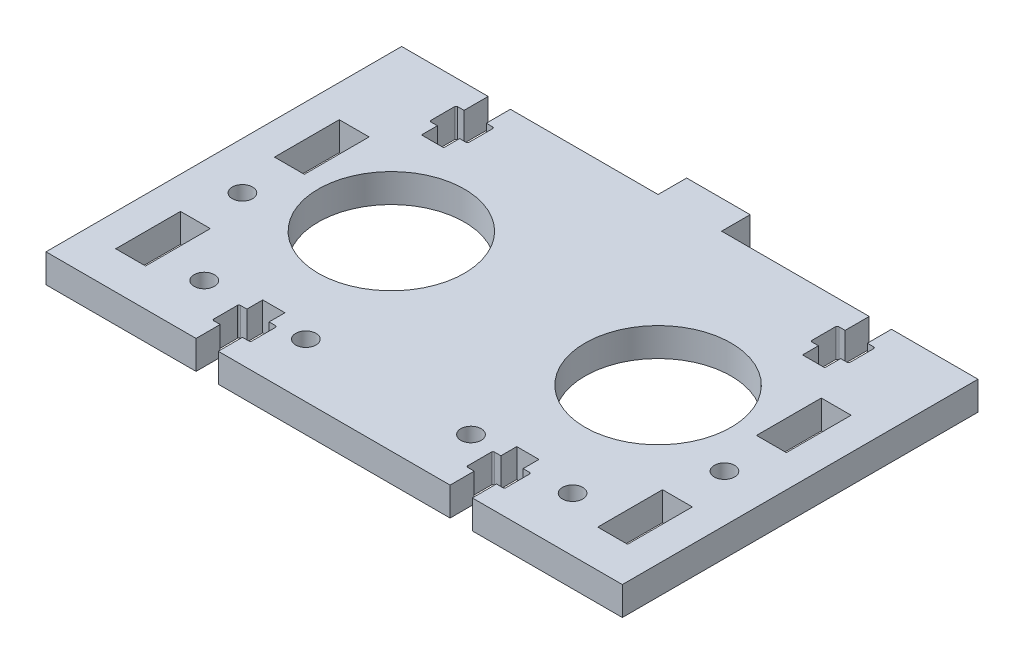
SolidWorks part; units mm, degrees
ref_plane "Front Plane" through (0, 0, 0) normal (0, 0, 1) x (1, 0, 0)
ref_plane "Top Plane" through (0, 0, 0) normal (0, 1, 0) x (1, 0, 0)
ref_plane "Right Plane" through (0, 0, 0) normal (1, 0, 0) x (0, 0, -1)
sketch "Sketch1" plane through (0, 0, 0) normal (0, 1, 0) x (1, 0, 0)
  line L1 (-45.375, 28) -> (45.375, 28)
  line L2 (-45.375, 28) -> (-45.375, -28)
  line L3 (-45.375, -28) -> (45.375, -28)
  line L4 (45.375, 28) -> (45.375, -28)
  line L5 (-45.375, 28) -> (45.375, -28) construction
  line L6 (-45.375, -28) -> (45.375, 28) construction
  point P0 (0, 0)
  dimension "D1" = 90.75
  dimension "D2" = 56
extrude "MainShape" add sketch "Sketch1" along normal blind 4.5
sketch "Sketch2" plane through (0, 4.5, 0) normal (0, 1, 0) x (1, 0, 0)
  line L0 (0, -28) -> (0, 28) construction
  line L1 (-45.375, -28) -> (45.375, -28) construction
  line L2 (45.375, 28) -> (-45.375, 28) construction
  line L4 (-5, 32.5) -> (5, 32.5)
  line L5 (-5, 32.5) -> (-5, 23.5)
  line L6 (-5, 23.5) -> (5, 23.5)
  line L7 (5, 32.5) -> (5, 23.5)
  line L8 (-5, 32.5) -> (5, 23.5) construction
  line L9 (-5, 23.5) -> (5, 32.5) construction
  dimension "D2" = 4.5
extrude "Tab1" add sketch "Sketch2" against normal through all
sketch "Sketch4" plane through (0, 4.5, 0) normal (0, 1, 0) x (1, 0, 0)
  line L0 (0, 32.5) -> (0, -28) construction
  line L1 (5, 32.5) -> (-5, 32.5) construction
  line L2 (-45.375, -28) -> (45.375, -28) construction
  line L3 (-30, 28) -> (-30, 17.5) construction
  line L4 (-5, 28) -> (-45.375, 28) construction
  line L5 (-28.25, 17.5) -> (-31.75, 17.5) construction
  line L6 (-31.75, 17.5) -> (-31.75, 28) construction
  line L7 (-28.25, 17.5) -> (-31.75, 17.5)
  line L8 (-31.75, 17.5) -> (-31.75, 20)
  line L9 (-31.75, 20) -> (-32.75, 20)
  line L10 (-33, 20.25) -> (-33, 23.95)
  line L11 (-32.75, 24.2) -> (-31.75, 24.2)
  line L12 (-31.75, 24.2) -> (-31.75, 28)
  line L13 (-31.75, 28) -> (-28.25, 28)
  line L14 (-28.25, 17.5) -> (-28.25, 28) construction
  line L15 (-28.25, 24.2) -> (-28.25, 28)
  line L16 (-27.25, 24.2) -> (-28.25, 24.2)
  line L17 (-27, 20.25) -> (-27, 23.95)
  line L18 (-28.25, 20) -> (-27.25, 20)
  line L19 (-28.25, 17.5) -> (-28.25, 20)
  line L20 (28.25, 17.5) -> (28.25, 28) construction
  line L21 (31.75, 17.5) -> (31.75, 28) construction
  line L22 (28.25, 17.5) -> (31.75, 17.5) construction
  line L23 (30, 28) -> (30, 17.5) construction
  line L24 (28.25, 17.5) -> (28.25, 20)
  line L25 (28.25, 20) -> (27.25, 20)
  line L26 (27, 20.25) -> (27, 23.95)
  line L27 (27.25, 24.2) -> (28.25, 24.2)
  line L28 (28.25, 24.2) -> (28.25, 28)
  line L29 (31.75, 28) -> (28.25, 28)
  line L30 (31.75, 24.2) -> (31.75, 28)
  line L31 (32.75, 24.2) -> (31.75, 24.2)
  line L32 (33, 20.25) -> (33, 23.95)
  line L33 (31.75, 20) -> (32.75, 20)
  line L34 (31.75, 17.5) -> (31.75, 20)
  line L35 (28.25, 17.5) -> (31.75, 17.5)
  arc A0 (-32.75, 20) -> (-33, 20.25) centre (-32.75, 20.25) cw
  arc A1 (-27, 20.25) -> (-27.25, 20) centre (-27.25, 20.25) cw
  arc A2 (-27.25, 24.2) -> (-27, 23.95) centre (-27.25, 23.95) cw
  arc A3 (-33, 23.95) -> (-32.75, 24.2) centre (-32.75, 23.95) cw
  arc A4 (33, 23.95) -> (32.75, 24.2) centre (32.75, 23.95) ccw
  arc A5 (27.25, 24.2) -> (27, 23.95) centre (27.25, 23.95) ccw
  arc A6 (27, 20.25) -> (27.25, 20) centre (27.25, 20.25) ccw
  arc A7 (32.75, 20) -> (33, 20.25) centre (32.75, 20.25) ccw
  point P24 (-33, 20)
  point P27 (-27, 20)
  point P30 (-27, 24.2)
  point P33 (-33, 24.2)
  point P56 (33, 24.2)
  point P57 (27, 24.2)
  point P58 (27, 20)
  point P59 (33, 20)
  dimension "D7" = 0.25
  dimension "D1" = 10.5
  dimension "D2" = 1.75
  dimension "D3" = 4.2
  dimension "D4" = 3
  dimension "D5" = 8
  dimension "D6" = 30
extrude "Cut-Extrude2" cut sketch "Sketch4" against normal through all
sketch "Sketch5" plane through (0, 4.5, 0) normal (0, 1, 0) x (1, 0, 0)
  line L0 (0, -28) -> (0, 32.5) construction
  line L1 (-45.375, -28) -> (45.375, -28) construction
  line L2 (5, 32.5) -> (-5, 32.5) construction
  line L3 (37.95, 28) -> (37.95, -28) construction
  line L4 (45.375, 28) -> (31.75, 28) construction
  line L5 (-37.95, 28) -> (-37.95, -28) construction
  line L6 (35.6, 13.1) -> (40.3, 13.1)
  line L7 (35.6, 13.1) -> (35.6, 2.9)
  line L8 (35.6, 2.9) -> (40.3, 2.9)
  line L9 (40.3, 13.1) -> (40.3, 2.9)
  line L10 (35.6, 13.1) -> (40.3, 2.9) construction
  line L11 (35.6, 2.9) -> (40.3, 13.1) construction
  line L12 (-35.6, 2.9) -> (-40.3, 13.1) construction
  line L13 (-35.6, 13.1) -> (-40.3, 2.9) construction
  line L14 (-40.3, 13.1) -> (-40.3, 2.9)
  line L15 (-35.6, 2.9) -> (-40.3, 2.9)
  line L16 (-35.6, 13.1) -> (-35.6, 2.9)
  line L17 (-35.6, 13.1) -> (-40.3, 13.1)
  line L18 (-45.375, -4.5) -> (45.375, -4.5) construction
  line L19 (-45.375, 28) -> (-45.375, -28) construction
  line L20 (45.375, -28) -> (45.375, 28) construction
  line L21 (-35.6, -22.1) -> (-40.3, -11.9) construction
  line L22 (-35.6, -11.9) -> (-40.3, -22.1) construction
  line L23 (35.6, -11.9) -> (40.3, -22.1) construction
  line L24 (35.6, -22.1) -> (40.3, -11.9) construction
  line L25 (-35.6, -22.1) -> (-40.3, -22.1)
  line L26 (-35.6, -22.1) -> (-35.6, -11.9)
  line L27 (-35.6, -11.9) -> (-40.3, -11.9)
  line L28 (-40.3, -22.1) -> (-40.3, -11.9)
  line L29 (40.3, -22.1) -> (40.3, -11.9)
  line L30 (35.6, -11.9) -> (40.3, -11.9)
  line L31 (35.6, -22.1) -> (35.6, -11.9)
  line L32 (35.6, -22.1) -> (40.3, -22.1)
  line L33 (-35.6, 13.1) -> (-40.3, 2.9) construction
  circle A0 centre (37.95, -4.5) radius 1.6
  circle A1 centre (-37.95, -4.5) radius 1.6
  point P10 (37.95, 8)
  point P21 (-37.95, 8)
  point P36 (-37.95, -17)
  point P37 (37.95, -17)
  dimension "D6" = 3.2
  dimension "D1" = 37.95
  dimension "D2" = 10.2
  dimension "D3" = 4.7
  dimension "D4" = 20
  dimension "D5" = 25
extrude "Cut-Extrude3" cut sketch "Sketch5" against normal through all
sketch "Sketch6" plane through (0, 4.5, 0) normal (0, 1, 0) x (1, 0, 0)
  line L0 (-21, -28) -> (-21, 28) construction
  line L2 (5, 32.5) -> (-5, 32.5) construction
  line L3 (-45.375, 2) -> (45.375, 2) construction
  line L4 (-45.375, 28) -> (-45.375, -28) construction
  line L5 (45.375, -28) -> (45.375, 28) construction
  line L6 (45.375, 28) -> (31.75, 28) construction
  line L7 (-45.375, -28) -> (45.375, -28) construction
  line L9 (-45.375, 28) -> (45.375, 28) construction
  circle A0 centre (-21, 2) radius 11.5
  point P4 (0, 32.5)
  dimension "D1" = 23
  dimension "D2" = 26
extrude "Cut-Extrude4" cut sketch "Sketch6" against normal through all
sketch "Sketch8" plane through (0, 4.5, 0) normal (0, 1, 0) x (1, 0, 0)
  line L0 (-32.5, 2) -> (-9.5, 2) construction
  line L1 (-21, 2) -> (-21, -19.46) construction
  line L2 (-13, -19.46) -> (-29, -19.46) construction
  line L3 (-21, -9.5) -> (-21, 13.5) construction
  circle A0 centre (-29, -19.46) radius 1.6
  circle A1 centre (-21, 2) radius 11.5 construction
  circle A2 centre (-13, -19.46) radius 1.6
  dimension "D3" = 3.2
  dimension "D1" = 90
  dimension "D2" = 8
  dimension "D4" = 21.46
extrude "Cut-Extrude6" cut sketch "Sketch8" against normal through all
sketch "Sketch9" plane through (0, 4.5, 0) normal (0, 1, 0) x (1, 0, 0)
  line L0 (0, -28) -> (0, 32.5) construction
  line L1 (-45.375, -28) -> (45.375, -28) construction
  line L2 (5, 32.5) -> (-5, 32.5) construction
  line L3 (20, -28) -> (20, -17.5) construction
  line L4 (18.25, -17.5) -> (21.75, -17.5) construction
  line L5 (21.75, -17.5) -> (21.75, -28) construction
  line L6 (21.75, -28) -> (21.75, -24.2)
  line L7 (21.75, -24.2) -> (22.75, -24.2)
  line L8 (23, -23.95) -> (23, -20.25)
  line L9 (22.75, -20) -> (21.75, -20)
  line L10 (21.75, -20) -> (21.75, -17.5)
  line L11 (21.75, -17.5) -> (18.25, -17.5)
  line L12 (21.75, -28) -> (18.25, -28)
  line L13 (18.25, -17.5) -> (18.25, -28) construction
  line L14 (18.25, -20) -> (18.25, -17.5)
  line L15 (17.25, -20) -> (18.25, -20)
  line L16 (17, -23.95) -> (17, -20.25)
  line L17 (18.25, -24.2) -> (17.25, -24.2)
  line L18 (18.25, -28) -> (18.25, -24.2)
  line L19 (-18.25, -17.5) -> (-18.25, -28) construction
  line L20 (-21.75, -17.5) -> (-21.75, -28) construction
  line L21 (-18.25, -17.5) -> (-21.75, -17.5) construction
  line L22 (-20, -28) -> (-20, -17.5) construction
  line L23 (-18.25, -28) -> (-18.25, -24.2)
  line L24 (-18.25, -24.2) -> (-17.25, -24.2)
  line L25 (-17, -23.95) -> (-17, -20.25)
  line L26 (-17.25, -20) -> (-18.25, -20)
  line L27 (-18.25, -20) -> (-18.25, -17.5)
  line L28 (-21.75, -28) -> (-18.25, -28)
  line L29 (-21.75, -17.5) -> (-18.25, -17.5)
  line L30 (-21.75, -20) -> (-21.75, -17.5)
  line L31 (-22.75, -20) -> (-21.75, -20)
  line L32 (-23, -23.95) -> (-23, -20.25)
  line L33 (-21.75, -24.2) -> (-22.75, -24.2)
  line L34 (-21.75, -28) -> (-21.75, -24.2)
  arc A0 (22.75, -24.2) -> (23, -23.95) centre (22.75, -23.95) ccw
  arc A1 (23, -20.25) -> (22.75, -20) centre (22.75, -20.25) ccw
  arc A2 (17, -20.25) -> (17.25, -20) centre (17.25, -20.25) cw
  arc A3 (17.25, -24.2) -> (17, -23.95) centre (17.25, -23.95) cw
  arc A4 (-17.25, -24.2) -> (-17, -23.95) centre (-17.25, -23.95) ccw
  arc A5 (-17, -20.25) -> (-17.25, -20) centre (-17.25, -20.25) ccw
  arc A6 (-23, -20.25) -> (-22.75, -20) centre (-22.75, -20.25) cw
  arc A7 (-22.75, -24.2) -> (-23, -23.95) centre (-22.75, -23.95) cw
  point P16 (23, -24.2)
  point P19 (23, -20)
  point P30 (17, -20)
  point P31 (17, -24.2)
  point P54 (-17, -24.2)
  point P55 (-17, -20)
  point P56 (-23, -20)
  point P57 (-23, -24.2)
  dimension "D7" = 0.25
  dimension "D1" = 10.5
  dimension "D2" = 1.75
  dimension "D3" = 8
  dimension "D4" = 4.2
  dimension "D5" = 3
  dimension "D6" = 20
extrude "Cut-Extrude7" cut sketch "Sketch9" against normal through all
sketch "Sketch10" [suppressed] plane through (0, 0, 28) normal (0, 0, 1) x (1, 0, 0)
  line L0 (-55, 2.25) -> (55, 2.25) construction
  line L1 (-55, 4.5) -> (-55, 0) construction
  line L2 (55, 4.5) -> (55, 0) construction
  line L3 (-16, 4.5) -> (-16, 0) construction
  line L4 (-14.25, 4.5) -> (-17.75, 4.5) construction
  line L5 (16, 4.5) -> (16, 0) construction
  line L6 (17.75, 4.5) -> (14.25, 4.5) construction
  line L7 (17.75, 0) -> (14.25, 0) construction
  line L8 (-14.25, 0) -> (-17.75, 0) construction
  circle A0 centre (-16, 2.25) radius 1.6
  circle A1 centre (16, 2.25) radius 1.6
  dimension "D1" = 3.2
  dimension "D2" = 3.2
mirror "Mirror1" about plane through (0, 0, 0) normal (1, 0, 0) of "Cut-Extrude6", "Cut-Extrude4"
equation "\"X-ROD-SPACING\"=45"
equation "\"Y-ROD-SPACING\"=75"
equation "\"Z-ROD-SPACING\"=17.5"
equation "\"Y-BED-OFFSET\"=2"
equation "\"Y-BED-ROD-INSET\"=3.5"
equation "\"Y-BED-SCREW-SPACING\"=209"
equation "\"Y-BED-SCREW-CUTOUT-SLOT-HEIGHT\"=1"
equation "\"T-SLOT-NUT-FILLET-RADIUS\"=0.25"
equation "\"T-SLOT-SCREW-SHAFT-RADIUS\"=1.75"
equation "\"T-SLOT-SCREW-SHAFT-CUTOUT-LENGTH\"=10.5"
equation "\"T-SLOT-NUT-DEPTH\"=4.2"
equation "\"T-SLOT-NUT-WIDTH\"=3"
equation "\"T-SLOT-NUT-END-DISTANCE\"=8"
equation "\"ACRYLIC-THICKNESS\"=10"
equation "\"ACRYLIC-THICKNESS2\"=4.5"
equation "\"ACRYLIC-TAB-CUTOUT-SIZE\"=\"ACRYLIC-THICKNESS\"+\"ACRYLIC-TAB-TOLERANCE\"*2"
equation "\"ACRYLIC-TAB-WIDTH\"=\"ACRYLIC-THICKNESS\""
equation "\"ACRYLIC-M3-HOLE\"=3.2"
equation "\"SMOOTHROD-CAP-SCREW-DISTANCE\"=20"
equation "\"FRAME-WIDTH-INNER\"=370"
equation "\"NEMA17-HOLE-SPACING\"=31"
equation "\"NEMA17-CENTRAL-CUTOUT\"=22.5"
equation "\"Z-BRACKET-REACH\"=55"
equation "\"Z-ROD-INSET\"=16"
equation "\"TOP-BRACKET-SPACING\"=40"
equation "\"SMOOTHROD-X-LENGTH\"=350"
equation "\"SMOOTHROD-Y-LENGTH\"=350"
equation "\"SMOOTHROD-Z-LENGTH\"=350"
equation "\"SMOOTHROD-TIGHTENING-HEADROOM\"=1"
equation "\"LEADSCREW-Z-LENGTH\"=300"
equation "\"SCREW-LENGTH-FRAME\"=\"ACRYLIC-THICKNESS\" + 10"
equation "\"SCREW-LENGTH-MOTOR\"=\"ACRYLIC-THICKNESS\" + 5"
equation "\"SCREW-LENGTH-EXTRUDER\"=28"
equation "\"SCREW-HEAD-RADIUS\"=6"
equation "\"PRINTED-X-SMOOTHROD-DIAMETER\"=8.2"
equation "\"PRINTED-X-SMOOTHROD-CUTOUT\"=10"
equation "\"PRINTED-X-BASE-HEIGHT\"=10"
equation "\"PRINTED-LM8UU-CUTOUT-SIZE\"=16"
equation "\"PRINTED-LM8UU-CUTOUT-LENGTH\"=24.5"
equation "\"PRINTED-X-IDLER-HEIGHT\"=16"
equation "\"PSU-MOUNTING-WIDTH\"=95"
equation "\"PSU-MOUNTING-HEIGHT\"=177"
equation "\"Y-BELT-TO-ROD-DISTANCE\"=20"
equation "\"SPOOL-HOLDER-ROD-SPACING\"=150"
equation "\"ACRYLIC-X-CARRIAGE-WIDTH\"=55"
equation "\"ACRYLIC-X-CARRIAGE-HEIGHT\"=75"
equation "\"ACRYLIC-X-CARRIAGE-SCREW-SPACING-X\"=15"
equation "\"ACRYLIC-X-CARRIAGE-SCREW-SPACING-Y\"=33"
equation "\"ACRYLIC-X-CARRIAGE-CENTER-TAB-SPACING\"=14"
equation "\"D1@Sketch1\"=\"ACRYLIC-X-CARRIAGE-WIDTH\"*\"ACRYLIC-X-CARRIAGE-DUAL-WIDTH-MULTIPLIER\""
equation "\"D1@MainShape\" = \"ACRYLIC-THICKNESS2\""
equation "\"D1@Sketch2\"=\"ACRYLIC-TAB-WIDTH\""
equation "\"D2@Sketch2\"=\"ACRYLIC-THICKNESS2\""
equation "\"D1@Sketch4\"=\"T-SLOT-SCREW-SHAFT-CUTOUT-LENGTH\""
equation "\"D2@Sketch4\"=\"T-SLOT-SCREW-SHAFT-RADIUS\""
equation "\"D3@Sketch4\"=\"T-SLOT-NUT-DEPTH\""
equation "\"D4@Sketch4\"=\"T-SLOT-NUT-WIDTH\""
equation "\"D5@Sketch4\"=\"T-SLOT-NUT-END-DISTANCE\""
equation "\"D6@Sketch4\"=\"ACRYLIC-X-CARRIAGE-SCREW-SPACING-X\"*2"
equation "\"D7@Sketch4\"=\"T-SLOT-NUT-FILLET-RADIUS\""
equation "\"ACRYLIC-X-CARRIAGE-EXTRUDER-SHELF-DEPTH\"=\"ACRYLIC-X-CARRIAGE-EXTRUDER-OFFSET\" + 30"
equation "\"D2@Sketch1\"=\"ACRYLIC-X-CARRIAGE-EXTRUDER-SHELF-DEPTH\""
equation "\"ACRYLIC-X-CARRIAGE-LM8UU-CUTOUT-WIDTH\"=24.25"
equation "\"ACRYLIC-X-CARRIAGE-EXTRUDER-BRACE-SPACING\"=23"
equation "\"ACRYLIC-X-CARRIAGE-EXTRUDER-BRACE-TAB-OFFSET\"=20"
equation "\"ACRYLIC-X-CARRIAGE-EXTRUDER-BRACE-HEIGHT\"=35"
equation "\"ACRYLIC-X-CARRIAGE-EXTRUDER-BRACE-SCREW-SPACING\"=22"
equation "\"D1@Sketch5\"=\"ACRYLIC-X-CARRIAGE-EXTRUDER-BRACE-SPACING\"*\"ACRYLIC-X-CARRIAGE-DUAL-WIDTH-MULTIPLIER\""
equation "\"D2@Sketch5\"=\"ACRYLIC-TAB-CUTOUT-SIZE\""
equation "\"D3@Sketch5\"=\"ACRYLIC-THICKNESS2\"+\"ACRYLIC-TAB-TOLERANCE\"*2"
equation "\"D4@Sketch5\"=\"ACRYLIC-X-CARRIAGE-EXTRUDER-BRACE-TAB-OFFSET\""
equation "\"D3@Sketch8\"=\"ACRYLIC-M3-HOLE\""
equation "\"ACRYLIC-X-CARRIAGE-EXTRUDER-ANGLE\"=90"
equation "\"D1@Sketch8\"=\"ACRYLIC-X-CARRIAGE-EXTRUDER-ANGLE\""
equation "\"ACRYLIC-X-CARRIAGE-EXTRUDER-OFFSET\"=26"
equation "\"D2@Sketch6\"=\"ACRYLIC-X-CARRIAGE-EXTRUDER-OFFSET\""
equation "\"D6@Sketch5\"=\"ACRYLIC-M3-HOLE\""
equation "\"D1@Sketch9\"=\"T-SLOT-SCREW-SHAFT-CUTOUT-LENGTH\""
equation "\"D2@Sketch9\"=\"T-SLOT-SCREW-SHAFT-RADIUS\""
equation "\"D3@Sketch9\"=\"T-SLOT-NUT-END-DISTANCE\""
equation "\"D4@Sketch9\"=\"T-SLOT-NUT-DEPTH\""
equation "\"D5@Sketch9\"=\"T-SLOT-NUT-WIDTH\""
equation "\"D7@Sketch9\"=\"T-SLOT-NUT-FILLET-RADIUS\""
equation "\"ACRYLIC-TAB-TOLERANCE\"=.1"
equation "\"ACRYLIC-X-CARRIAGE-DUAL-WIDTH-MULTIPLIER\"=1.65"
equation "\"ACRYLIC-X-CARRIAGE-DUAL-HOTEND-SPACING\"=42"
equation "\"D4@Sketch6\"=\"ACRYLIC-X-CARRIAGE-DUAL-HOTEND-SPACING\"/2"
